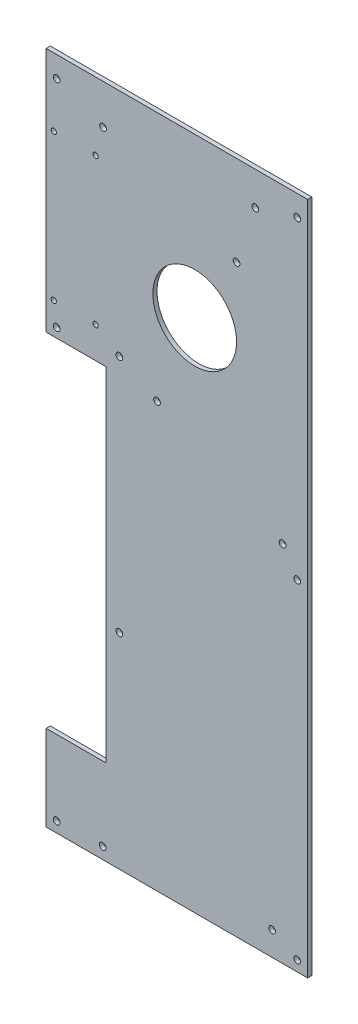
SolidWorks part; units mm, degrees
ref_plane "Front Plane" through (0, 0, 0) normal (1, 0, 0) x (0, 1, 0)
ref_plane "Top Plane" through (0, 0, 0) normal (0, 0, 1) x (0, 1, 0)
ref_plane "Right Plane" through (0, 0, 0) normal (0, 1, 0) x (-1, 0, 0)
sketch "Sketch1" plane through (0, 0, 0) normal (0, 0, 1) x (0, 1, 0)
  line L0 (-57.15, 6.35) -> (-57.15, 35)
  line L1 (-98, 6.35) -> (224.3, 6.35)
  line L2 (-98, 6.35) -> (-98, -90)
  line L3 (-98, -90) -> (224.3, -90)
  line L4 (224.3, 6.35) -> (224.3, -90)
  line L5 (-57.15, 35) -> (-98, 35)
  line L6 (-98, 35) -> (-98, 6.35)
  line L7 (196.85, 6.35) -> (196.85, 35)
  line L8 (196.85, 35) -> (224.3, 35)
  line L9 (224.3, 35) -> (224.3, 6.35)
  line L10 (196.85, 35) -> (106.85, 35)
  line L11 (121.85, 31.35) -> (191.85, 31.35) construction
  line L12 (121.85, 31.35) -> (121.85, 11.35) construction
  line L13 (121.85, 11.35) -> (191.85, 11.35) construction
  line L14 (191.85, 31.35) -> (191.85, 11.35) construction
  line L15 (106.85, 35) -> (106.85, 6.35)
  circle A0 centre (-86.5, -73) radius 1.6
  circle A1 centre (-92.5, 8) radius 1.6
  circle A2 centre (0, 0) radius 1.6
  circle A3 centre (114.3, 0) radius 1.6
  circle A4 centre (104.8, -18) radius 1.6
  circle A5 centre (181.3, -56) radius 1.6
  circle A6 centre (208.3, -65) radius 1.6
  circle A7 centre (205.3, 7.8) radius 1.6
  circle A8 centre (75.7, -78) radius 1.6
  circle A18 centre (148.3, -36) radius 20
  circle A19 centre (-93, 30) radius 1.6
  circle A20 centre (-93, -85) radius 1.6
  circle A21 centre (214.3, -85) radius 1.6
  circle A22 centre (214.3, 30) radius 1.6
  circle A23 centre (121.85, 31.35) radius 1.25
  circle A24 centre (121.85, 11.35) radius 1.25
  circle A25 centre (191.85, 11.35) radius 1.25
  circle A26 centre (191.85, 31.35) radius 1.25
  circle A27 centre (111.3, 30) radius 1.6
  circle A28 centre (64.3, -85) radius 1.6
  point P51 (0, 0)
  dimension "D1" = 3.2
  dimension "D13" = 78
  dimension "D23" = 3.2
  dimension "D26" = 34
  dimension "D27" = 40
  dimension "D29" = 5
  dimension "D34" = 2.5
  dimension "D38" = 103
  dimension "D39" = 150
  dimension "D2" = 114.3
  dimension "D3" = 8
  dimension "D4" = 92.5
  dimension "D5" = 73
  dimension "D6" = 86.5
  dimension "D7" = 98
  dimension "D8" = 110
  dimension "D9" = 91
  dimension "D10" = 7.8
  dimension "D11" = 94
  dimension "D12" = 65
  dimension "D14" = 38.6
  dimension "D15" = 9.5
  dimension "D16" = 18
  dimension "D17" = 67
  dimension "D18" = 56
  dimension "D19" = 90
  dimension "D20" = 6.35
  dimension "D21" = 57.15
  dimension "D22" = 35
  dimension "D24" = 5
  dimension "D25" = 82.55
  dimension "D28" = 36
  dimension "D30" = 5
  dimension "D31" = 10
  dimension "D32" = 20
  dimension "D33" = 70
  dimension "D35" = 5
  dimension "D36" = 5
  dimension "D37" = 15
extrude "Boss-Extrude1" add sketch "Sketch1" against normal blind 2 contours A7 L1 L2 L3 L4 A21 A20 A18 A8 A6 A5 A4 A3 A2 A0 | L5 L6 L1 L0 A19 A1 | A7 L1 L9 L8 L7 A22 | L10 L15 L1 L7 A26 A25 A24 A23 region at (-20.6983, -77.3635, 0) region at (42.0372, 59.5074, 0) region at (-20.6404, 151.9394, 0) region at (-20.7095, 210.5902, 0)
